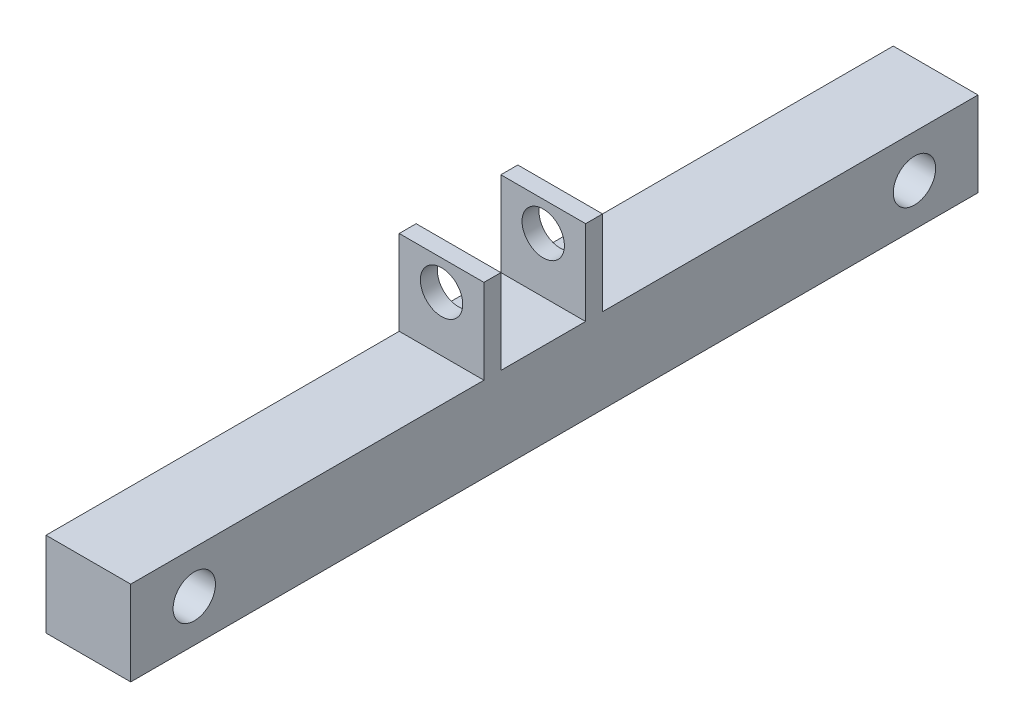
SolidWorks part; units mm, degrees
ref_plane "Front Plane" through (0, 0, 0) normal (0, 0, 1) x (1, 0, 0)
ref_plane "Top Plane" through (0, 0, 0) normal (0, 1, 0) x (1, 0, 0)
ref_plane "Right Plane" through (0, 0, 0) normal (1, 0, 0) x (0, 0, -1)
sketch "Sketch1" plane through (0, 0, 0) normal (0, 0, 1) x (1, 0, 0)
  line L1 (-10, 10) -> (10, 10)
  line L2 (-10, 10) -> (-10, -10)
  line L3 (-10, -10) -> (10, -10)
  line L4 (10, 10) -> (10, -10)
  line L5 (-10, 10) -> (10, -10) construction
  line L6 (-10, -10) -> (10, 10) construction
  circle A0 centre (0, 0) radius 5 construction
  point P1 (0, 0)
  dimension "D3" = 10
  dimension "D1" = 20
  dimension "D2" = 20
extrude "Boss-Extrude1" add sketch "Sketch1" along normal blind 200
sketch "Sketch2" plane through (0, 10, 0) normal (0, 1, 0) x (1, 0, 0)
  line L0 (0, -200) -> (0, 0) construction
  line L1 (10, -200) -> (-10, -200) construction
  line L2 (-10, -100) -> (10, -100) construction
  line L3 (-10, -200) -> (-10, 0) construction
  line L4 (10, -200) -> (10, 0) construction
  circle A0 centre (0, -100) radius 7.5
  dimension "D1" = 15
sketch "Sketch3" plane through (-10, 0, 0) normal (-1, 0, 0) x (0, 0, 1)
  line L0 (0, 0) -> (200, 0) construction
  line L1 (200, 10) -> (200, -10) construction
  line L2 (0, 10) -> (0, -10) construction
  line L3 (100, 10) -> (100, -10) construction
  line L4 (200, 10) -> (0, 10) construction
  line L5 (200, -10) -> (0, -10) construction
  circle A0 centre (15, 0) radius 5
  circle A1 centre (185, 0) radius 5
  dimension "D1" = 10
  dimension "D2" = 15
extrude "Cut-Extrude1" cut sketch "Sketch3" against normal blind 57
sketch "Sketch4" plane through (0, 10, 0) normal (0, 1, 0) x (1, 0, 0)
  line L0 (-10, -100) -> (-10, -92.6259)
  line L1 (-10, -200) -> (-10, 0) construction
  line L2 (-10, -92.6259) -> (10, -92.6259)
  line L3 (10, -200) -> (10, 0) construction
  line L4 (10, -92.6259) -> (10, -112.6259)
  line L5 (10, -112.6259) -> (-10, -112.6259)
  line L6 (-10, -112.6259) -> (-10, -100)
  line L7 (10, -116.6259) -> (-10, -116.6259)
  line L8 (-10, -116.6259) -> (-10, -112.6259)
  line L9 (10, -116.6259) -> (10, -112.6259)
  line L10 (10, -88.6259) -> (-10, -88.6259)
  line L11 (-10, -88.6259) -> (-10, -92.6259)
  line M8 (-10, 0) -> (-10, -200)
  line M10 (10, -200) -> (10, 0)
  dimension "D1" = 20
  dimension "D2" = 4
  dimension "D3" = 4
extrude "Boss-Extrude2" add sketch "Sketch4" along normal blind 20 contours L7 L5 M10 M8 | L10 L2 M10 M8 region at (0, 10, 90.6259) region at (0, 10, 114.6259)
sketch "Sketch5" plane through (0, 0, 88.6259) normal (0, 0, -1) x (-1, 0, 0)
  line L0 (0, 30) -> (0, 10) construction
  line L1 (-10, 30) -> (10, 30) construction
  line L2 (7.5, 10) -> (-7.5, 10) construction
  line L3 (0, 10) -> (0, 23) construction
  line L4 (0, 23) -> (10, 23) construction
  line L6 (10, 23) -> (-10, 23) construction
  line L9 (-10, 10) -> (10, 10) construction
  circle A0 centre (0, 23) radius 5
  dimension "D1" = 10
  dimension "D2" = 13
extrude "Cut-Extrude2" cut sketch "Sketch5" against normal blind 49
